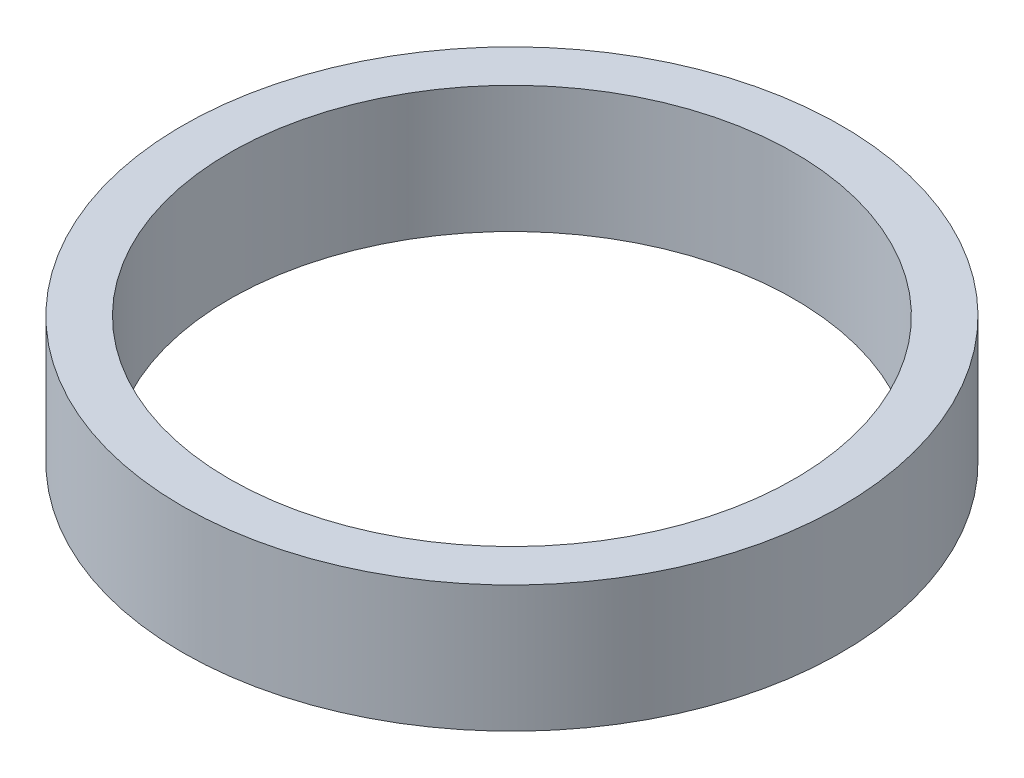
SolidWorks part; units mm, degrees
ref_plane "Front Plane" through (0, 0, 0) normal (0, 0, 1) x (1, 0, 0)
ref_plane "Top Plane" through (0, 0, 0) normal (0, 1, 0) x (1, 0, 0)
ref_plane "Right Plane" through (0, 0, 0) normal (1, 0, 0) x (0, 0, -1)
ref_axis "Axis1" through (0, 0, 0) along (0, 1, 0)
sketch "Sketch1" plane through (0, 0, 0) normal (0, 0, 1) x (1, 0, 0)
  line L0 (0, 0) -> (0, -12944.9559) construction
  line L1 (-6, 4.25) -> (-7, 4.25)
  line L2 (-6, 4.25) -> (-6, 1.56)
  line L3 (-6, 1.56) -> (-7, 1.56)
  line L4 (-7, 4.25) -> (-7, 1.56)
  line L6 (-7.5467, 4.25) -> (7.5467, 4.25) construction
  line L7 (7.5467, 1.56) -> (-7.5467, 1.56) construction
  dimension "D1" = 12
  dimension "D2" = 1
revolve "Revolve1" add sketch "Sketch1" angle 360 about L0
